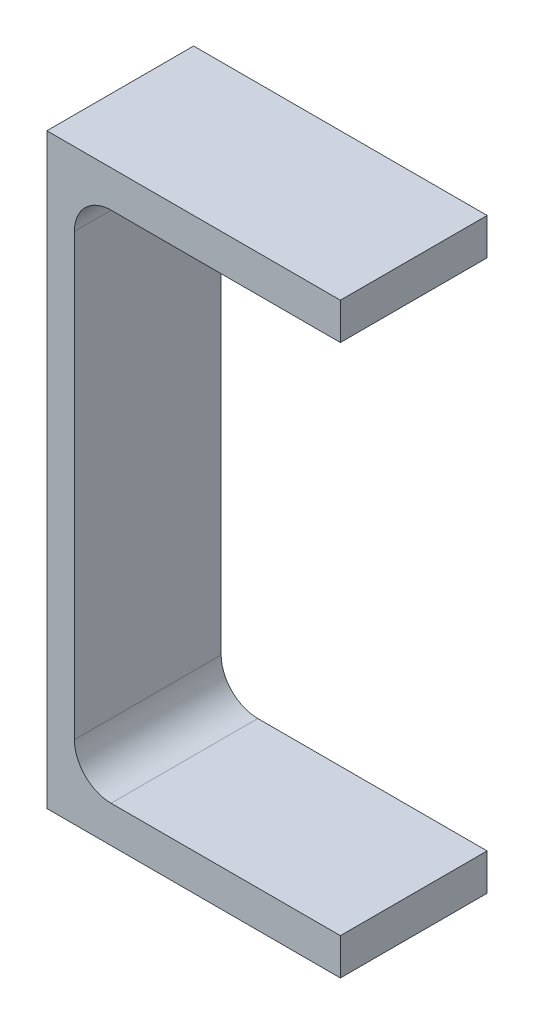
SolidWorks part; units mm, degrees
ref_plane "Plane1" through (0, 0, 0) normal (0, 0, 1) x (1, 0, 0)
ref_plane "Plane2" through (0, 0, 0) normal (0, 1, 0) x (1, 0, 0)
ref_plane "Plane3" through (0, 0, 0) normal (1, 0, 0) x (0, 0, -1)
sketch "Sketch1" plane through (0, 0, 0) normal (0, 0, 1) x (1, 0, 0)
  line L0 (0, 0) -> (0, 101.6)
  line L2 (4.7625, 88.9) -> (4.7625, 12.7)
  line L3 (11.1125, 6.35) -> (50.8, 6.35)
  line L4 (50.8, 12.7) -> (50.8, 0) construction
  line L5 (50.8, 0) -> (0, 0)
  line L6 (50.8, 101.6) -> (0, 101.6)
  line L7 (50.8, 0) -> (50.8, 6.35)
  line L8 (50.8, 101.6) -> (50.8, 95.25)
  line L9 (11.1125, 95.25) -> (50.8, 95.25)
  arc A0 (4.7625, 88.9) -> (11.1125, 95.25) centre (11.1125, 88.9) cw
  arc A2 (11.1125, 6.35) -> (4.7625, 12.7) centre (11.1125, 12.7) cw
  dimension "D1" = 6.35
  dimension "Thickness" = 6.35
extrude "BaseChannelse" add sketch "Sketch1" along normal mid plane 25.4
equation "\"D1@Sketch1\" = \"Thickness@Sketch1\""
